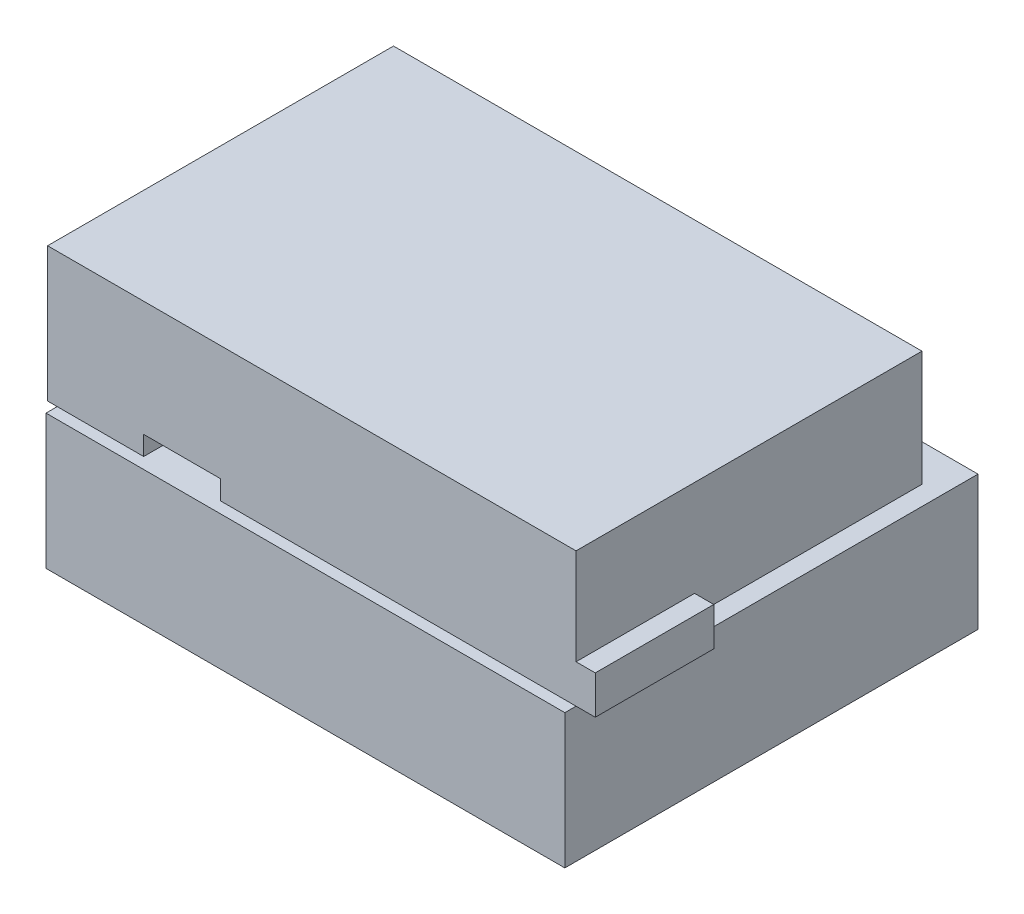
SolidWorks part; units mm, degrees
ref_plane "Front Plane" through (0, 0, 0) normal (0, 0, 1) x (1, 0, 0)
ref_plane "Top Plane" through (0, 0, 0) normal (0, 1, 0) x (1, 0, 0)
ref_plane "Right Plane" through (0, 0, 0) normal (1, 0, 0) x (0, 0, -1)
ref_plane "Plane1" through (0, 15, 0) normal (0, 1, 0) x (1, 0, 0)
sketch "Sketch2" plane through (0, 0, 0) normal (0, 1, 0) x (1, 0, 0)
  line L1 (-27, -21.5) -> (27, -21.5)
  line L2 (-27, -21.5) -> (-27, 21.5)
  line L3 (-27, 21.5) -> (27, 21.5)
  line L4 (27, -21.5) -> (27, 21.5)
  line L5 (-27, -21.5) -> (27, 21.5) construction
  line L6 (-27, 21.5) -> (27, -21.5) construction
  point P0 (0, 0)
  dimension "D1" = 54
  dimension "D2" = 43
extrude "Boss-Extrude1-Battery" add sketch "Sketch2" along normal blind 14
sketch "Sketch4" plane through (0, 15, 0) normal (0, 1, 0) x (1, 0, 0)
  line L1 (-27, -21.3333) -> (28, -21.3333)
  line L2 (-27, -21.3333) -> (-27, 14.6667)
  line L3 (-27, 14.6667) -> (28, 14.6667)
  line L4 (28, -21.3333) -> (28, 14.6667)
  line L5 (-27, -21.3333) -> (28, 14.6667) construction
  line L6 (-27, 14.6667) -> (28, -21.3333) construction
  point P0 (0, 0)
  dimension "D1" = 55
  dimension "D2" = 36
extrude "Boss-Extrude2-Circuit" add sketch "Sketch4" along normal blind 14
sketch "Sketch8" plane through (0, 0, 21.3333) normal (0, 0, 1) x (1, 0, 0)
  line L1 (28, 15) -> (-9, 15)
  line L2 (28, 15) -> (28, 17)
  line L3 (28, 17) -> (-9, 17)
  line L4 (-9, 15) -> (-9, 17)
  line L6 (-9, 17) -> (-9, 15)
  line L7 (-9, 15) -> (-27, 15)
  line L8 (-27, 17) -> (-27, 15)
  line L9 (-27, 17) -> (-17, 17)
  line L10 (-27, 17) -> (-27, 15)
  line L11 (-27, 15) -> (-17, 15)
  line L12 (-17, 17) -> (-17, 15)
  line L13 (-17, 17) -> (-9, 17)
  line L14 (-17, 17) -> (-17, 15)
  line L15 (-17, 15) -> (-9, 15)
  line L16 (-9, 17) -> (-9, 15)
  dimension "D1" = 2
  dimension "D2" = 37
  dimension "D4" = 10
sketch "Sketch11" plane through (28, 0, 0) normal (1, 0, 0) x (0, 0, -1)
  line L0 (14.6667, 29) -> (14.6667, 15) construction
  line L1 (-21.3333, 15) -> (-12.3333, 15)
  line L2 (-21.3333, 15) -> (-21.3333, 17)
  line L3 (-21.3333, 17) -> (-12.3333, 17)
  line L4 (-12.3333, 15) -> (-12.3333, 17)
  line L5 (-12.3333, 15) -> (14.6667, 15)
  line L6 (-12.3333, 15) -> (-12.3333, 17)
  line L7 (-12.3333, 17) -> (14.6667, 17)
  line L8 (14.6667, 15) -> (14.6667, 17)
  line M3 (-21.3333, 15) -> (14.6667, 15)
  line M4 (14.6667, 15) -> (14.6667, 29)
  dimension "D1" = 9
  dimension "D2" = 2
extrude "Cut-Extrude2" cut sketch "Sketch11" against normal blind 55 contours L7 L4 M3 M4 region at (28, 16, -1.1667)
sketch "Sketch12" plane through (28, 0, 0) normal (1, 0, 0) x (0, 0, -1)
  line L1 (-21.3333, 15) -> (-9, 15)
  line L2 (-21.3333, 15) -> (-21.3333, 19)
  line L3 (-21.3333, 19) -> (-9, 19)
  line L4 (-9, 15) -> (-9, 19)
  dimension "D1" = 4
extrude "Boss-Extrude1" add sketch "Sketch12" along normal blind 2
extrude "Cut-Extrude3" cut sketch "Sketch8" against normal blind 10 contours L13 L12 L7 L4 region at (-13, 16, 21.3333)
